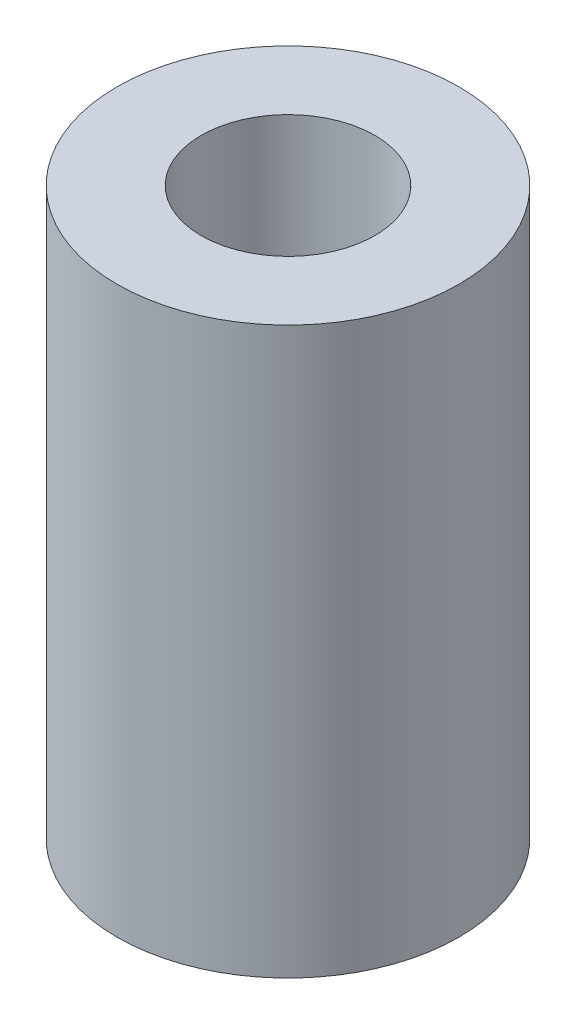
SolidWorks part; units mm, degrees
ref_plane "Front Plane" through (0, 0, 0) normal (0, 0, 1) x (1, 0, 0)
ref_plane "Top Plane" through (0, 0, 0) normal (0, 1, 0) x (1, 0, 0)
ref_plane "Right Plane" through (0, 0, 0) normal (1, 0, 0) x (0, 0, -1)
sketch "Sketch1" plane through (0, 0, 0) normal (0, 1, 0) x (1, 0, 0)
  circle A0 centre (0, 0) radius 6.35
  arc A4 (2.8735, 5.6626) -> (-4.861, -4.0858) centre (0, 0) ccw construction
  circle A5 centre (0, 0) radius 3.2258
  circle A6 centre (0, 0) radius 3.2258
  dimension "D1" = 0.0508
extrude "Boss-Extrude1" add sketch "Sketch1" along normal up to surface (21.0005 mm away)
